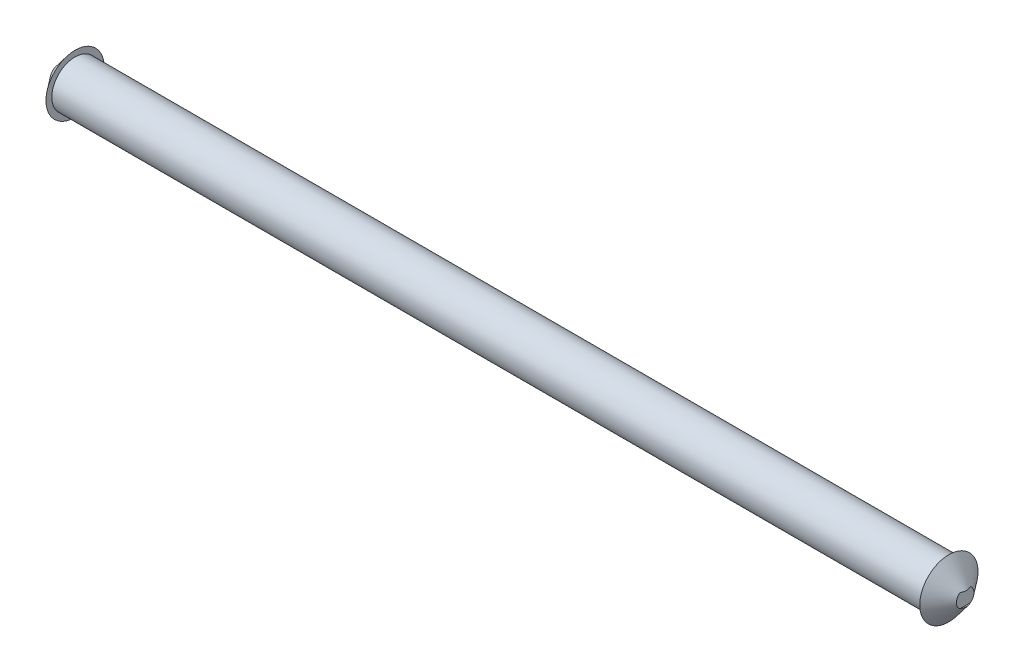
SolidWorks part; units mm, degrees
material "2219-T37"
ref_plane "Front Plane" through (0, 0, 0) normal (0, 0, 1) x (1, 0, 0)
ref_plane "Top Plane" through (0, 0, 0) normal (0, 1, 0) x (1, 0, 0)
ref_plane "Right Plane" through (0, 0, 0) normal (1, 0, 0) x (0, 0, -1)
sketch "Sketch1" plane through (0, 0, 0) normal (1, 0, 0) x (0, 0, -1)
  circle A0 centre (0, 0) radius 10
  dimension "D1" = 20
extrude "Boss-Extrude1" add sketch "Sketch1" along normal mid plane 375
ref_plane "Plane1" through (197.5, 0, 0) normal (1, 0, 0) x (0, 0, -1)
sketch "Sketch2" plane through (197.5, 0, 0) normal (1, 0, 0) x (0, 0, -1)
  point P0 (0, 0)
sketch "Sketch3" plane through (187.5, 0, 0) normal (1, 0, 0) x (0, 0, -1)
  circle A0 centre (0, 0) radius 12.5
  dimension "D1" = 25
loft "Loft1" add profiles "Sketch2", "Sketch3"
mirror "Mirror1" about plane through (0, 0, 0) normal (1, 0, 0) of "Loft1"
sketch "Sketch4" plane through (0, 0, 0) normal (0, 0, 1) x (1, 0, 0)
  line L1 (198.4923, -3) -> (194.4923, -3)
  line L2 (198.4923, -3) -> (198.4923, 3)
  line L3 (198.4923, 3) -> (194.4923, 3)
  line L4 (194.4923, -3) -> (194.4923, 3)
  point P4 (194.4923, 0)
  dimension "D1" = 6
  dimension "D2" = 4
  dimension "D3" = 194.4923
extrude "Cut-Extrude1" cut sketch "Sketch4" against normal through all and the other way blind 10
mirror "Mirror2" about plane through (0, 0, 0) normal (1, 0, 0) of "Cut-Extrude1"
